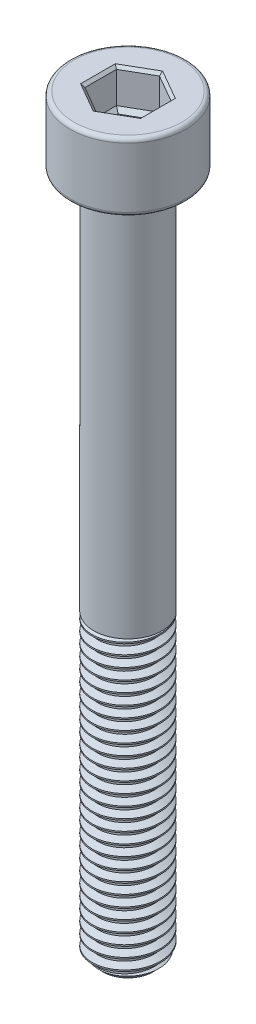
SolidWorks part; units mm, degrees
material "AISI Type A2 Tool Steel"
ref_plane "Front Plane" through (0, 0, 0) normal (0, 0, 1) x (1, 0, 0)
ref_plane "Top Plane" through (0, 0, 0) normal (0, 1, 0) x (1, 0, 0)
ref_plane "Right Plane" through (0, 0, 0) normal (1, 0, 0) x (0, 0, -1)
sketch "Sketch1" plane through (0, 0, 0) normal (0, 1, 0) x (1, 0, 0)
  circle A0 centre (0, 0) radius 2.5
  dimension "D1" = 5
extrude "Boss-Extrude1" add sketch "Sketch1" along normal blind 22
thread "Thread1" pitch 0.8 start angle 0, offset 1, length 0, pitch 0.8, diameter 5
ref_plane "Plane1" through (-2.5, 23, 0) normal (0, 0, 1) x (-1, 0, 0)
sketch "Thread Profile1" plane through (-2.5, 23, 0) normal (0, 0, 1) x (-1, 0, 0)
  line L0 (0, 0) -> (0, 0.8) construction
  line L11 (0, 0) -> (0, 0.7)
  line L12 (0, 0.7) -> (-0.433, 0.45)
  line L13 (-0.433, 0.45) -> (-0.433, 0.25)
  line L15 (-0.433, 0.25) -> (0, 0)
  line L17 (-0.433, 0.35) -> (0, 0.35) construction
  point P2 (0, 0)
  dimension "Pitch" = 0.8
  dimension "Profile_Angle" = 60
  dimension "Profile_Land" = 0.2
  dimension "Profile_Height" = 0.433
sketch "Sketch2" plane through (0, 22, 0) normal (0, 1, 0) x (1, 0, 0)
  circle A0 centre (0, 0) radius 2.5
  dimension "D1" = 5
extrude "Boss-Extrude2" add sketch "Sketch2" along normal blind 28
sketch "Sketch3" plane through (0, 50, 0) normal (0, 1, 0) x (1, 0, 0)
  circle A0 centre (0, 0) radius 4.25
  dimension "D1" = 8.5
extrude "Boss-Extrude3" add sketch "Sketch3" along normal blind 5
fillet "Fillet1" radius 0.3 2 edges at (0, 50, 4.25) (0, 55, 4.25)
sketch "Sketch4" plane through (0, 0, 0) normal (0, 0, 1) x (1, 0, 0)
  line L0 (0, 0) -> (0, 0.4416) construction
  line L1 (0, 0) -> (2.51, 0) construction
  line L2 (2.51, 0) -> (2.51, 0.7)
  line L3 (2.51, 0.7) -> (1.81, 0)
  line L4 (1.81, 0) -> (2.51, 0)
  dimension "D1" = 0.7
  dimension "D2" = 45
  dimension "D3" = 2.51
revolve "Cut-Revolve1" cut sketch "Sketch4" angle 360 about L0
sketch "Sketch5" plane through (0, 55, 0) normal (0, 1, 0) x (1, 0, 0)
  line L1 (0, 2.3094) -> (-2, 1.1547)
  line L2 (-2, 1.1547) -> (-2, -1.1547)
  line L3 (-2, -1.1547) -> (0, -2.3094)
  line L4 (0, -2.3094) -> (2, -1.1547)
  line L5 (2, -1.1547) -> (2, 1.1547)
  line L6 (2, 1.1547) -> (0, 2.3094)
  circle A0 centre (0, 0) radius 2 construction
  dimension "D1" = 4
extrude "Cut-Extrude1" cut sketch "Sketch5" against normal blind 2.5
chamfer "Chamfer1" distance 0.2 angle 45 6 edges at (-1, 55, 1.7321) (1, 55, 1.7321) (2, 55, 0) (1, 55, -1.7321) (-1, 55, -1.7321) (-2, 55, 0)
sketch "Sketch6" plane through (0, 52.5, 0) normal (0, 1, 0) x (1, 0, 0)
  line L1 (0, 2.3094) -> (-2, 1.1547)
  line L2 (-2, 1.1547) -> (-2, -1.1547)
  line L3 (-2, -1.1547) -> (0, -2.3094)
  line L4 (0, -2.3094) -> (2, -1.1547)
  line L5 (2, -1.1547) -> (2, 1.1547)
  line L6 (2, 1.1547) -> (0, 2.3094)
  circle A0 centre (0, 0) radius 2 construction
extrude "Cut-Extrude2" cut sketch "Sketch6" against normal blind 0.3 draft 45
